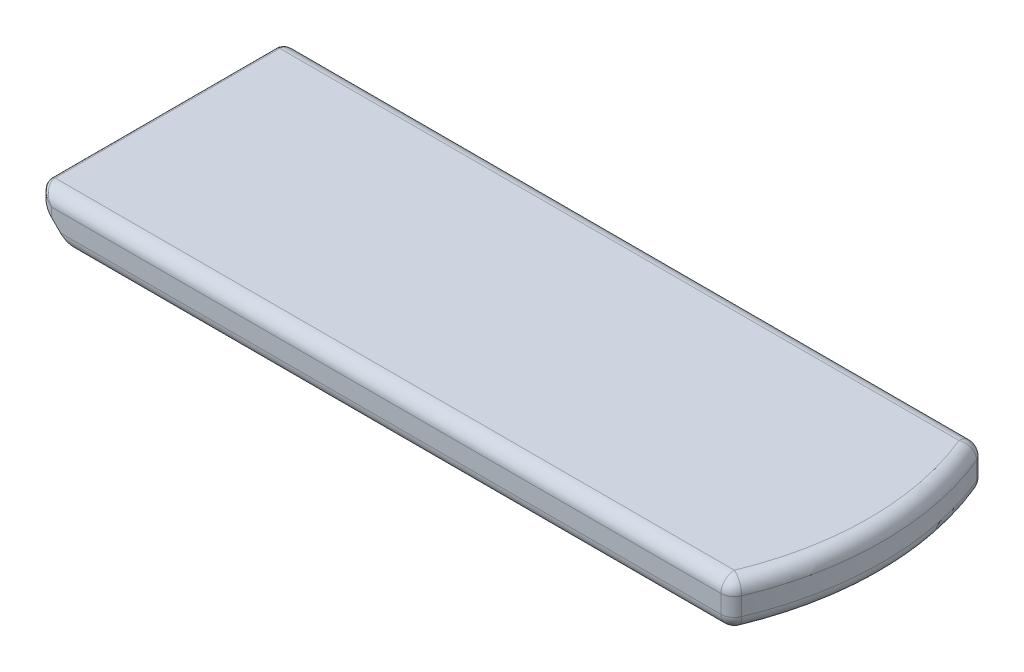
SolidWorks part; units mm, degrees
ref_plane "Front Plane" through (0, 0, 0) normal (0, 0, 1) x (1, 0, 0)
ref_plane "Top Plane" through (0, 0, 0) normal (0, 1, 0) x (1, 0, 0)
ref_plane "Right Plane" through (0, 0, 0) normal (1, 0, 0) x (0, 0, -1)
sketch "Sketch1" plane through (0, 0, 0) normal (1, 0, 0) x (0, 0, -1)
  line L1 (0, -1.591) -> (3.556, -1.591)
  line L2 (0, -1.591) -> (0, -2.226)
  line L3 (0, -2.226) -> (3.556, -2.226)
  line L4 (3.556, -1.591) -> (3.556, -2.226)
  dimension "D1" = 0.635
  dimension "D2" = 3.556
extrude "Extrude1" add sketch "Sketch1" along normal blind 10.16
chamfer "Chamfer1" distance 0.508 angle 45 1 edges at (0, -2.226, -1.778)
sketch "Sketch2" plane through (0, -2.226, 0) normal (0, -1, 0) x (1, 0, 0)
  line L0 (10.16, 0) -> (0.508, 0) construction
  line L1 (10.16, -3.556) -> (0.508, -3.556) construction
  line L2 (9.779, 0) -> (10.5928, 0)
  line L3 (10.5928, 0) -> (10.5928, -3.556)
  line L4 (10.5928, -3.556) -> (9.779, -3.556)
  line L5 (10.16, 0) -> (10.16, -3.556) construction
  arc A0 (9.779, 0) -> (9.779, -3.556) centre (5.8208, -1.778) cw
  point P3 (10.16, -1.778)
  point P13 (10.16, -1.778)
  dimension "D1" = 0.381
  dimension "D2" = 0.381
fillet "Fillet2" radius 0.0508 1 edges at (0, -1.591, -1.778)
extrude "Extrude3" cut sketch "Sketch2" against normal blind 9.144
fillet "Fillet3" radius 0.1905 13 edges at (0, -1.6799, 0) (0.0149, -1.6058, 0) (0, -1.6799, -3.556) (0.0149, -1.6058, -3.556) (10.16, -1.591, -1.778) (9.779, -1.9085, -3.556) (10.16, -2.226, -1.778) (9.779, -1.9085, 0) (0.508, -2.226, -1.778) (4.9149, -1.591, 0) (5.1435, -2.226, 0) (4.9149, -1.591, -3.556) (5.1435, -2.226, -3.556)
